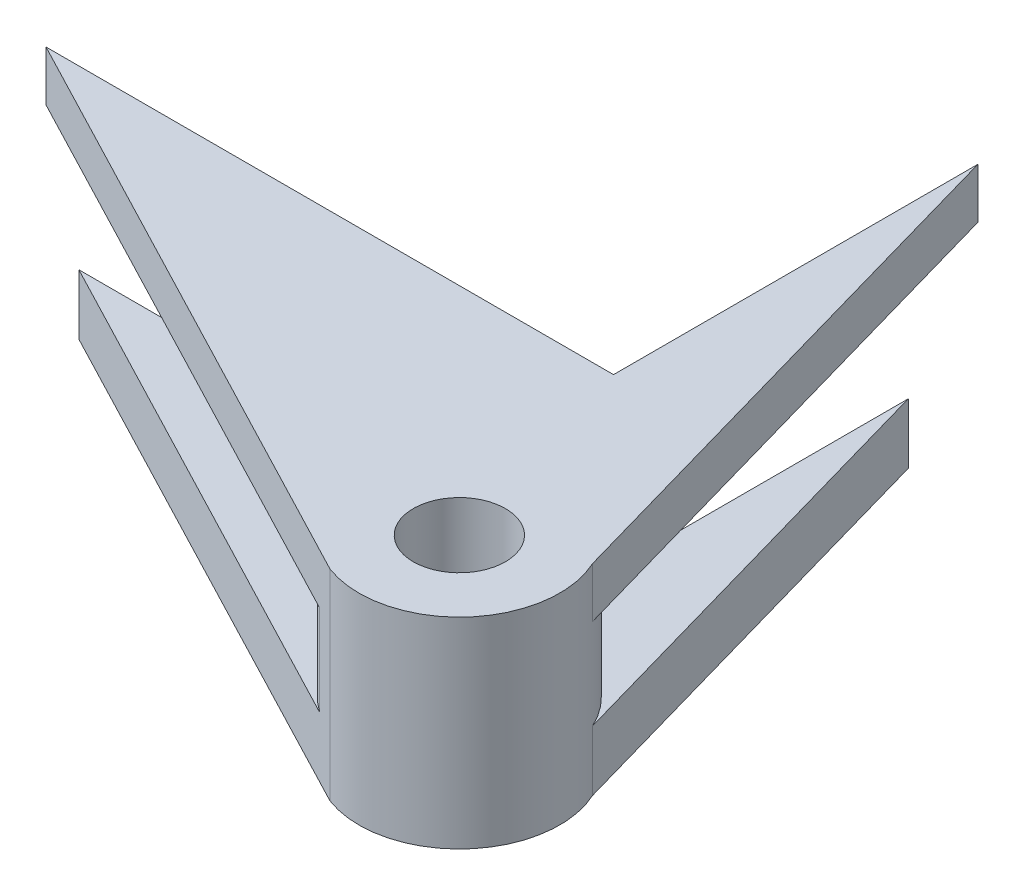
SolidWorks part; units mm, degrees
ref_plane "Front Plane" through (0, 0, 0) normal (0, 0, 1) x (1, 0, 0)
ref_plane "Top Plane" through (0, 0, 0) normal (0, 1, 0) x (1, 0, 0)
ref_plane "Right Plane" through (0, 0, 0) normal (1, 0, 0) x (0, 0, -1)
sketch "Sketch1" plane through (0, 0, 0) normal (0, 1, 0) x (1, 0, 0)
  line L0 (30.5988, 30.1673) -> (30.5988, 0)
  line L1 (30.5988, 30.1673) -> (43.0895, -13.7576)
  line L2 (0, 0) -> (-21.8247, 0)
  line L3 (-21.8247, 0) -> (30.4854, -27.3048)
  line L4 (30.5988, 0) -> (0, 0)
  circle A0 centre (34.009, -17.9461) radius 10
  circle A1 centre (34.009, -17.9461) radius 4.5901
  point P7 (-38.7691, 0)
  point P10 (-21.8247, 0)
  point P13 (30.5988, 30.1673)
  point P14 (0, 0)
  point P15 (43.0895, -13.7576)
  dimension "20" = 20
extrude "Boss-Extrude1" add sketch "Sketch1" along normal blind 6 contours A0 L1 L2 L3 region at (17.0461, 0, 4.7884)
extrude "Boss-Extrude2" add sketch "Sketch1<3>" along normal blind 20 contours A0 A1 region at (43.5001, 0, 15.8627)
sketch "Sketch1<3>" plane through (0, 0, 0) normal (0, 1, 0) x (1, 0, 0) same geometry as "Sketch1"
sketch "Sketch2" plane through (0, 20, 0) normal (0, 1, 0) x (1, 0, 0)
  line L0 (43.0895, -13.7576) -> (30.5988, 30.1673)
  line L1 (30.5988, 30.1673) -> (27.8398, 39.8693)
  line L2 (27.8398, 39.8693) -> (27.8398, 3.5758)
  line L3 (27.8398, 3.5758) -> (-28.6751, 3.5758)
  line L4 (-28.6751, 3.5758) -> (-21.8247, 0)
  line L5 (-21.8247, 0) -> (28.3455, -26.1878) construction
  line L6 (-21.8247, 0) -> (28.3455, -26.1878)
  circle A0 centre (34.009, -17.9461) radius 10
  arc M3 (30.4854, -27.3048) -> (28.3455, -26.1878) centre (34.009, -17.9461) ccw
extrude "Boss-Extrude3" add sketch "Sketch2" against normal blind 5 contours L4 L6 L0 L1 L2 L3 M3 region at (15.4303, 20, 1.7635)
